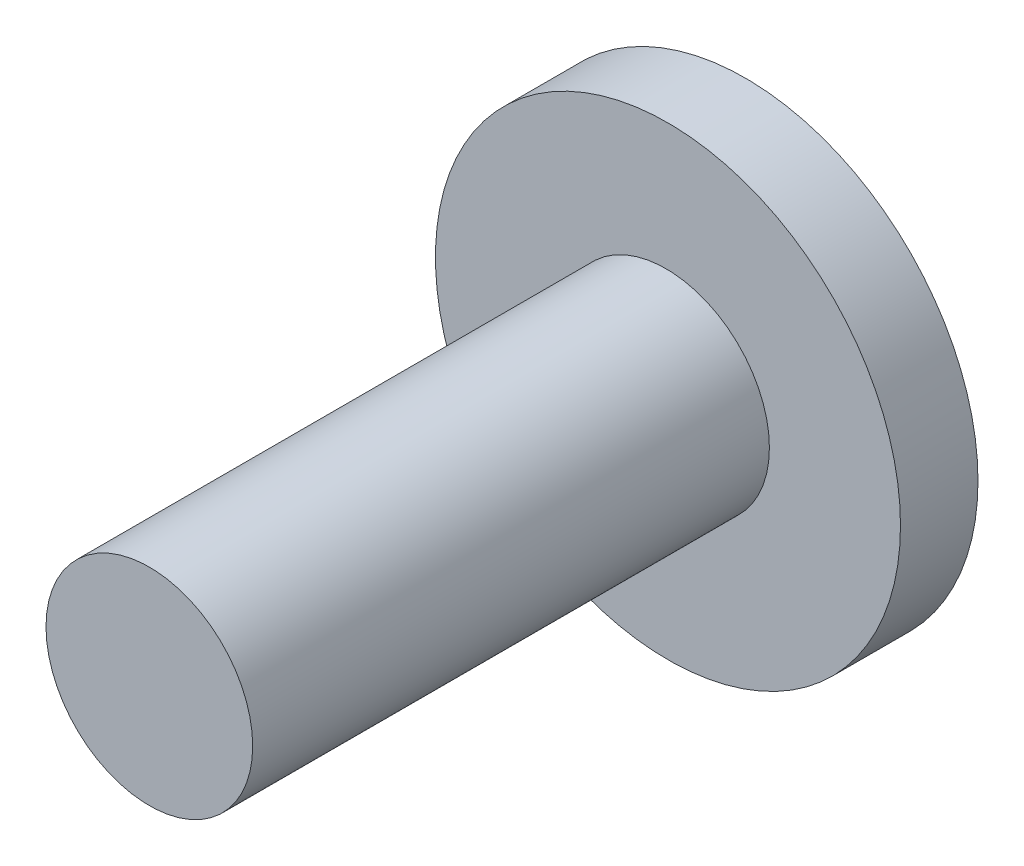
SolidWorks part; units mm, degrees
ref_plane "Front Plane" through (0, 0, 0) normal (0, 0, 1) x (1, 0, 0)
ref_plane "Top Plane" through (0, 0, 0) normal (0, 1, 0) x (1, 0, 0)
ref_plane "Right Plane" through (0, 0, 0) normal (1, 0, 0) x (0, 0, -1)
sketch "Sketch1" plane through (0, 0, 0) normal (0, 0, 1) x (1, 0, 0)
  line L0 (-2.1006, 1.75) -> (2.1421, 1.75)
  line L1 (-2.1006, -1.75) -> (2.1421, -1.75)
  arc A1 (2.1421, 1.75) -> (2.1421, -1.75) centre (0, 0) cw
  arc A2 (-2.1006, -1.75) -> (-2.1006, 1.75) centre (0.0037, 0) cw
  circle A3 centre (0, 0) radius 8
extrude "Boss-Extrude1" add sketch "Sketch1" along normal blind 2
sketch "Sketch2" plane through (0, 0, 2) normal (0, 0, 1) x (1, 0, 0)
  circle A2 centre (0, 0) radius 9
  circle A3 centre (0, 0) radius 9
  dimension "D1" = 1
extrude "Boss-Extrude2" add sketch "Sketch2" against normal blind 3
extrude "Cut-Extrude1" cut sketch "Sketch1<2>" against normal blind 10 and the other way blind 10.0001 contours A2 L1 A1 L0 region at (0.0175, 0, 0)
sketch "Sketch1<2>" plane through (0, 0, 0) normal (0, 0, 1) x (1, 0, 0) same geometry as "Sketch1"
extrude "Boss-Extrude3" add sketch "Sketch1<3>" along normal blind 2 and the other way blind 0.0001 contours A3
sketch "Sketch1<3>" plane through (0, 0, 0) normal (0, 0, 1) x (1, 0, 0) same geometry as "Sketch1"
sketch "Sketch3" plane through (0, 0, 2) normal (0, 0, 1) x (1, 0, 0)
  circle A0 centre (-0.0741, 0.0741) radius 4
extrude "Boss-Extrude4" add sketch "Sketch3" along normal blind 20
